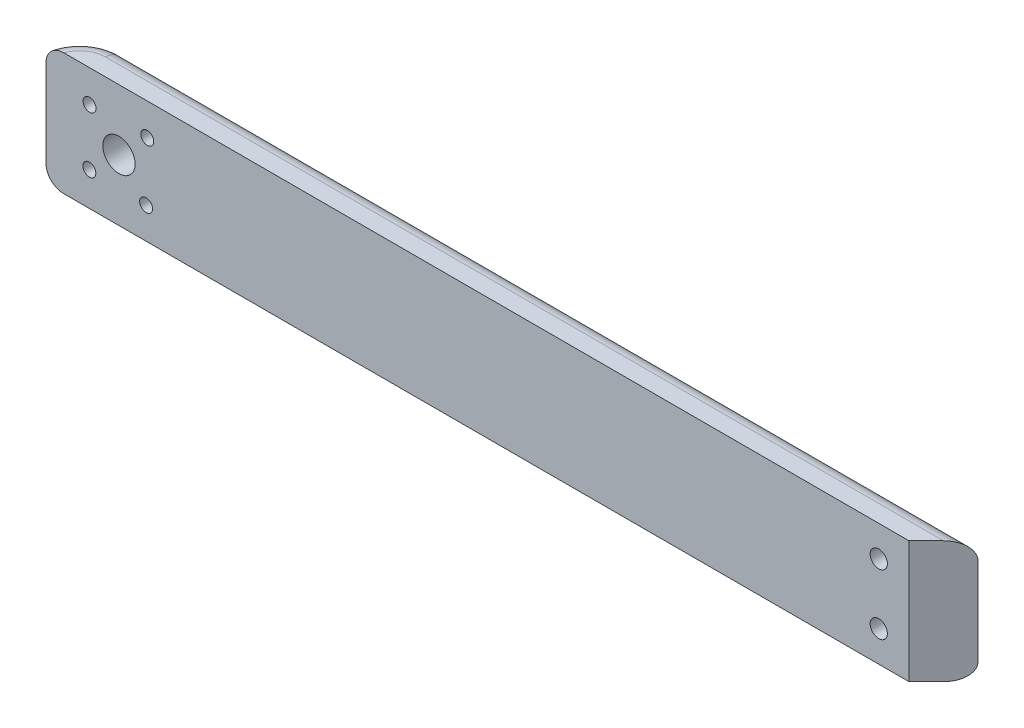
SolidWorks part; units mm, degrees
ref_plane "Plan de face" through (0, 0, 0) normal (0, 0, 1) x (1, 0, 0)
ref_plane "Plan de dessus" through (0, 0, 0) normal (0, 1, 0) x (1, 0, 0)
ref_plane "Plan de droite" through (0, 0, 0) normal (1, 0, 0) x (0, 0, -1)
sketch "Esquisse1" plane through (0, 0, 0) normal (0, 0, 1) x (1, 0, 0)
  line L1 (0, 0) -> (220, 0)
  line L2 (0, 0) -> (0, 28.284)
  line L3 (0, 28.284) -> (220, 28.284)
  line L4 (220, 0) -> (220, 28.284)
  dimension "D1" = 220
  dimension "D2" = 28.284
extrude "Boss.-Extru.3" add sketch "Esquisse1" along normal blind 8
chamfer "Chanfrein1" distance 20 angle 45 1 edges at (220, 14.142, 8)
sketch "Esquisse2" plane through (0, 0, 0) normal (0, 0, -1) x (-1, 0, 0)
  line L0 (-188, 28.284) -> (-188, 0)
  line L1 (-208, 28.284) -> (0, 28.284) construction
  line L2 (0, 0) -> (-208, 0) construction
  dimension "D1" = 20
sketch "Esquisse4" plane through (0, 0, 8) normal (0, 0, 1) x (1, 0, 0)
  line L0 (0, 0) -> (200, 0) construction
  line L2 (200, 0) -> (200, 28.284) construction
  line L5 (200, 28.284) -> (0, 28.284) construction
  circle A0 centre (193, 7.142) radius 2
  circle A1 centre (193, 21.142) radius 2
  dimension "D3" = 4
  dimension "D4" = 4
  dimension "D1" = 7.142
  dimension "D2" = 7.142
  dimension "D5" = 7
  dimension "D6" = 7
extrude "Enlèv. mat.-Extru.1" cut sketch "Esquisse4" against normal blind 8
fillet "Fillet1" radius 10 1 edges at (0, 14.142, 0)
sketch "Sketch2" plane through (0, 0, 8) normal (0, 0, 1) x (1, 0, 0)
  circle A0 centre (10.0393, 7.7998) radius 1.5
  circle A1 centre (10.0958, 20.8451) radius 1.5
  circle A2 centre (23.2048, 7.2432) radius 1.5
  circle A3 centre (23.4605, 20.8833) radius 1.5
  circle A4 centre (16.9035, 14.1779) radius 3.75
  point P2 (16.5315, 13.8323)
  dimension "D4" = 3
  dimension "D5" = 3
  dimension "D6" = 3
  dimension "D7" = 3
  dimension "D3" = 7.5
  dimension "D1" = 9.37
  dimension "D2" = 9.37
extrude "Cut-Extrude1" cut sketch "Sketch2" against normal blind 8
sketch "Sketch3" plane through (0, 0, 8) normal (0, 0, 1) x (1, 0, 0)
  circle A0 centre (17.5366, 14.6901) radius 2.1502
fillet "Fillet4" radius 4 2 edges at (108.899, 0, 0) (3.4734, 0, 2.254)
fillet "Fillet5" radius 4 2 edges at (108.899, 28.284, 0) (3.4734, 28.284, 2.254)
